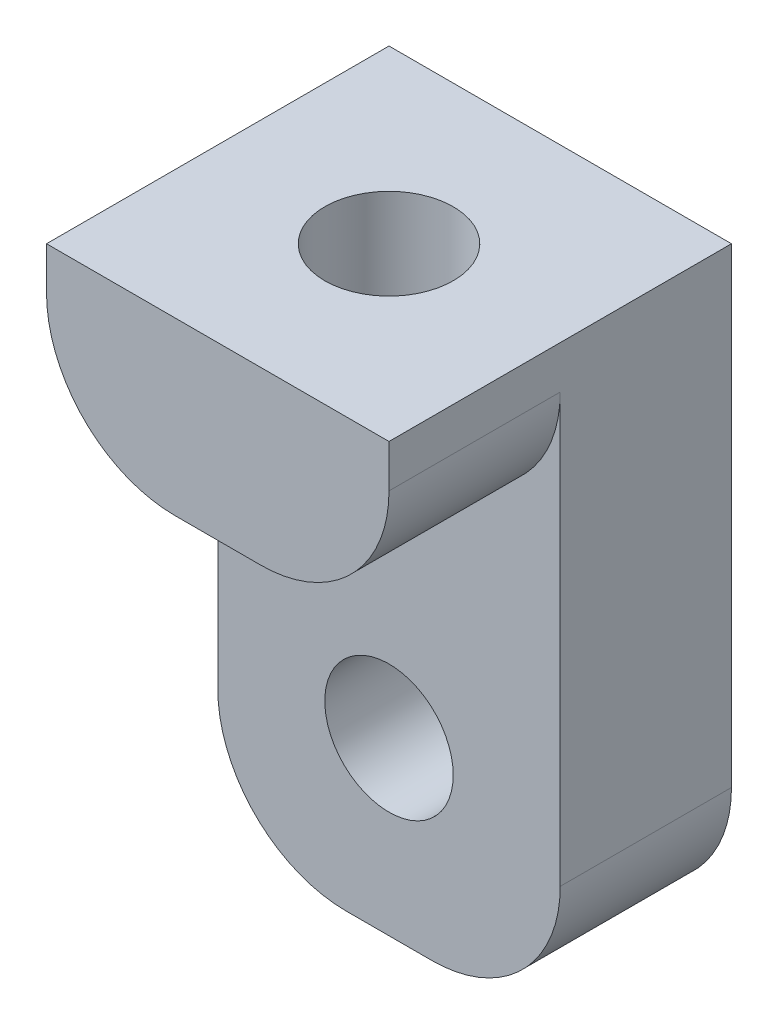
SolidWorks part; units mm, degrees
material "ABS"
ref_plane "Front Plane" through (0, 0, 0) normal (0, 0, 1) x (1, 0, 0)
ref_plane "Top Plane" through (0, 0, 0) normal (0, 1, 0) x (1, 0, 0)
ref_plane "Right Plane" through (0, 0, 0) normal (1, 0, 0) x (0, 0, -1)
sketch "Sketch1" plane through (0, 0, 0) normal (0, 0, 1) x (1, 0, 0)
  line L1 (-20, 50) -> (20, 50)
  line L2 (-20, 50) -> (-20, -20)
  line L3 (-20, -20) -> (20, -20)
  line L4 (20, 50) -> (20, -20)
  circle A0 centre (0, 0) radius 7.5
  point P6 (0, 0)
  point P8 (30.9278, -35.0258)
  point P9 (0, -20)
  point P10 (-25.8247, 54.201)
  dimension "D1" = 15
  dimension "D2" = 20
  dimension "D3" = 70
  dimension "D4" = 40
extrude "Boss-Extrude1" add sketch "Sketch1" along normal blind 40
sketch "Sketch2" plane through (0, 50, 0) normal (0, 1, 0) x (1, 0, 0)
  line L0 (-20, 0) -> (20, -40) construction
  line L4 (20, 0) -> (-20, 0)
  line L5 (-20, 0) -> (-20, -40)
  line L6 (-20, -40) -> (20, -40)
  line L7 (20, -40) -> (20, 0)
  line L8 (20, 0) -> (-20, 0)
  line L9 (-20, 0) -> (-20, -40)
  line L10 (-20, -40) -> (20, -40)
  line L11 (20, -40) -> (20, 0)
  circle A0 centre (0, -20) radius 7.5
  point P6 (0, -20)
  dimension "D2" = 15
  dimension "D1" = 0
extrude "Cut-Extrude1" cut sketch "Sketch2" against normal blind 20 contours L0 A0 | A0 L0 region at (2.2508, 50, 17.7492) region at (-2.2508, 50, 22.2508)
sketch "Sketch3" plane through (0, 0, 40) normal (0, 0, 1) x (1, 0, 0)
  line L0 (20, -20) -> (20, 50) construction
  line L1 (-20, -20) -> (20, -20)
  line L2 (-20, -20) -> (-20, 30)
  line L3 (-20, 30) -> (20, 30)
  line L4 (20, -20) -> (20, 30)
  dimension "D1" = 50
extrude "Cut-Extrude2" cut sketch "Sketch3" against normal blind 20 contours L2 L3 L4 L1
fillet "Fillet1" radius 15 4 edges at (-20, 30, 30) (20, 30, 30) (20, -20, 10) (-20, -20, 10)
